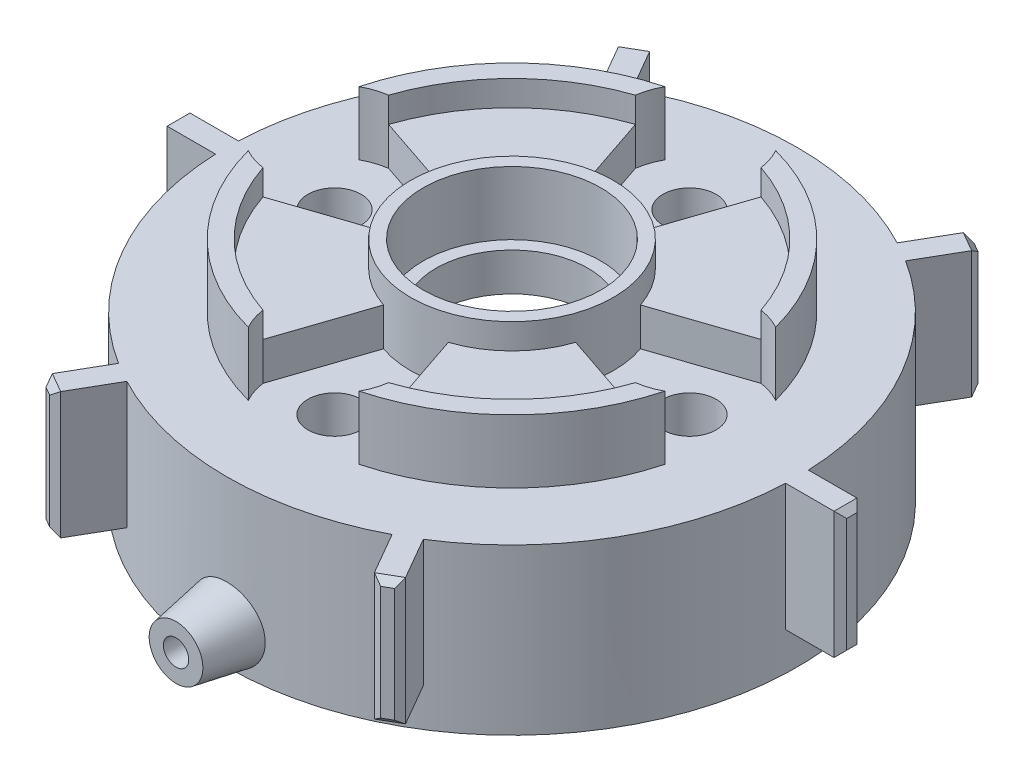
SolidWorks part; units mm, degrees
ref_plane "前视基准面" through (0, 0, 0) normal (0, 0, 1) x (1, 0, 0)
ref_plane "上视基准面" through (0, 0, 0) normal (0, 1, 0) x (1, 0, 0)
ref_plane "右视基准面" through (0, 0, 0) normal (1, 0, 0) x (0, 0, -1)
sketch "草图2" plane through (0, 0, 0) normal (0, 1, 0) x (1, 0, 0)
  line L0 (0, 30.8283) -> (0, -31.2236) construction
  line L1 (-31.2236, 0) -> (33.595, 0) construction
  circle A0 centre (0, 0) radius 22.5
  circle A1 centre (0, 0) radius 14 construction
  circle A2 centre (14, 0) radius 2.1
  circle A3 centre (0, 14) radius 2.1
  circle A4 centre (0, -14) radius 2.1
  circle A5 centre (-14, 0) radius 2.1
  circle A6 centre (0, 0) radius 6
  dimension "D1" = 45
  dimension "D2" = 4.2
  dimension "D3" = 4.2
  dimension "D4" = 28
  dimension "D5" = 12
extrude "凸台-拉伸1" add sketch "草图2" along normal blind 3
sketch "草图4" plane through (0, 0, 0) normal (0, -1, 0) x (1, 0, 0)
  circle A1 centre (0, 0) radius 22.5 construction
  circle A2 centre (0, 0) radius 22.5
  circle A3 centre (0, 0) radius 21
  dimension "D1" = 1.5
extrude "凸台-拉伸2" add sketch "草图4" along normal blind 10
sketch "草图5" plane through (0, 3, 0) normal (0, 1, 0) x (1, 0, 0)
  line L0 (-22.5, 0) -> (24.7317, 0) construction
  line L1 (0, 22.5) -> (0, -24.6712) construction
  line L2 (26.8, 0.9) -> (26.8, -0.9)
  line L3 (26.8, -0.9) -> (21, -0.9)
  line L4 (21, -0.9) -> (21, 0.9)
  line L5 (26.8, 0.9) -> (21, 0.9)
  line L6 (12.6206, -23.6595) -> (9.7206, -18.6365)
  line L7 (14.1794, -22.7595) -> (12.6206, -23.6595)
  line L8 (14.1794, -22.7595) -> (11.2794, -17.7365)
  line L9 (9.7206, -18.6365) -> (11.2794, -17.7365)
  line L10 (-14.1794, -22.7595) -> (-11.2794, -17.7365)
  line L11 (-12.6206, -23.6595) -> (-14.1794, -22.7595)
  line L12 (-12.6206, -23.6595) -> (-9.7206, -18.6365)
  line L13 (-11.2794, -17.7365) -> (-9.7206, -18.6365)
  line L14 (-26.8, 0.9) -> (-21, 0.9)
  line L15 (-26.8, -0.9) -> (-26.8, 0.9)
  line L16 (-26.8, -0.9) -> (-21, -0.9)
  line L17 (-21, 0.9) -> (-21, -0.9)
  line L18 (-12.6206, 23.6595) -> (-9.7206, 18.6365)
  line L19 (-14.1794, 22.7595) -> (-12.6206, 23.6595)
  line L20 (-14.1794, 22.7595) -> (-11.2794, 17.7365)
  line L21 (-9.7206, 18.6365) -> (-11.2794, 17.7365)
  line L22 (14.1794, 22.7595) -> (11.2794, 17.7365)
  line L23 (12.6206, 23.6595) -> (14.1794, 22.7595)
  line L24 (12.6206, 23.6595) -> (9.7206, 18.6365)
  line L25 (11.2794, 17.7365) -> (9.7206, 18.6365)
  circle A0 centre (0, 0) radius 22.5 construction
  point P14 (21, 0)
  point P15 (26.8, 0)
  dimension "D1" = 1.8
  dimension "D2" = 21
  dimension "D3" = 5.8
  dimension "D4" = 6
extrude "凸台-拉伸3" add sketch "草图5" against normal blind 10
sketch "草图6" plane through (0, 3, 0) normal (0, 1, 0) x (1, 0, 0)
  arc A0 (16.4286, 4.3706) -> (4.3706, 16.4286) centre (0, 0) ccw
  arc A1 (14.6875, 4.9525) -> (4.9525, 14.6875) centre (0, 0) ccw
  circle A2 centre (0, 0) radius 8
  circle A4 centre (0, 0) radius 7
  arc A7 (4.3706, -16.4286) -> (4.9525, -14.6875) centre (0, -14) ccw
  arc A8 (-14.6875, 4.9525) -> (-16.4286, 4.3706) centre (-14, 0) ccw
  arc A9 (16.4286, 4.3706) -> (14.6875, 4.9525) centre (14, 0) ccw
  arc A10 (4.9525, 14.6875) -> (4.3706, 16.4286) centre (0, 14) ccw
  arc A11 (14.6875, -4.9525) -> (16.4286, -4.3706) centre (14, 0) ccw
  arc A12 (4.3706, -16.4286) -> (16.4286, -4.3706) centre (0, 0) ccw
  arc A13 (4.9525, -14.6875) -> (14.6875, -4.9525) centre (0, 0) ccw
  arc A14 (-4.9525, -14.6875) -> (-4.3706, -16.4286) centre (0, -14) ccw
  arc A15 (-14.6875, -4.9525) -> (-4.9525, -14.6875) centre (0, 0) ccw
  arc A16 (-16.4286, -4.3706) -> (-14.6875, -4.9525) centre (-14, 0) ccw
  arc A17 (-16.4286, -4.3706) -> (-4.3706, -16.4286) centre (0, 0) ccw
  arc A18 (-4.9525, 14.6875) -> (-14.6875, 4.9525) centre (0, 0) ccw
  arc A19 (-4.3706, 16.4286) -> (-16.4286, 4.3706) centre (0, 0) ccw
  arc A20 (-4.3706, 16.4286) -> (-4.9525, 14.6875) centre (0, 14) ccw
  dimension "D1" = 16
  dimension "D2" = 1
  dimension "D3" = 31
  dimension "D4" = 1.5
  dimension "D5" = 10
  dimension "D6" = 10
  dimension "D7" = 10
  dimension "D8" = 10
extrude "凸台-拉伸4" add sketch "草图6" along normal blind 5
sketch "草图7" plane through (0, 3, 0) normal (0, 1, 0) x (1, 0, 0)
  line L0 (0, 22.5) -> (0, -29.8231) construction
  line L1 (29.3152, 0) -> (-30.7664, 0) construction
  line L2 (14.6875, -4.9525) -> (7.5806, -2.5561)
  line L3 (4.9525, -14.6875) -> (2.5561, -7.5806)
  line L4 (0, 0) -> (7.5806, -2.5561) construction
  line L5 (0, 0) -> (2.5561, -7.5806) construction
  line L6 (-4.9525, -14.6875) -> (-2.5561, -7.5806)
  line L7 (-14.6875, -4.9525) -> (-7.5806, -2.5561)
  line L8 (-14.6875, 4.9525) -> (-7.5806, 2.5561)
  line L9 (-4.9525, 14.6875) -> (-2.5561, 7.5806)
  line L10 (4.9525, 14.6875) -> (2.5561, 7.5806)
  line L11 (14.6875, 4.9525) -> (7.5806, 2.5561)
  arc A0 (10.4616, 19.92) -> (-10.4616, 19.92) centre (0, 0) ccw construction
  circle A1 centre (0, 0) radius 8 construction
  arc A2 (4.9525, -14.6875) -> (14.6875, -4.9525) centre (0, 0) ccw construction
  arc A4 (4.9525, -14.6875) -> (14.6875, -4.9525) centre (0, 0) ccw
  arc A5 (2.5561, -7.5806) -> (7.5806, -2.5561) centre (0, 0) ccw
  arc A6 (-2.5561, -7.5806) -> (-7.5806, -2.5561) centre (0, 0) cw
  arc A7 (-4.9525, -14.6875) -> (-14.6875, -4.9525) centre (0, 0) cw
  arc A8 (-4.9525, 14.6875) -> (-14.6875, 4.9525) centre (0, 0) ccw
  arc A9 (-2.5561, 7.5806) -> (-7.5806, 2.5561) centre (0, 0) ccw
  arc A10 (2.5561, 7.5806) -> (7.5806, 2.5561) centre (0, 0) cw
  arc A11 (4.9525, 14.6875) -> (14.6875, 4.9525) centre (0, 0) cw
extrude "凸台-拉伸5" add sketch "草图7" along normal blind 3
chamfer "倒角1" distance 0.5 angle 45 24 edges at (-12.6206, -2, 23.6595) (-13.4, -7, 23.2095) (-14.1794, -2, 22.7595) (-13.4, 3, 23.2095) (-26.8, -2, 0.9) (-26.8, -7, 0) (-26.8, -2, -0.9) (-26.8, 3, 0) (-14.1794, -2, -22.7595) (-13.4, -7, -23.2095) (-12.6206, -2, -23.6595) (-13.4, 3, -23.2095) (12.6206, -2, -23.6595) (13.4, -7, -23.2095) (14.1794, -2, -22.7595) (13.4, 3, -23.2095) (26.8, -2, -0.9) (26.8, -7, 0) (26.8, -2, 0.9) (26.8, 3, 0) (14.1794, -2, 22.7595) (13.4, -7, 23.2095) (12.6206, -2, 23.6595) (13.4, 3, 23.2095)
sketch "草图9" plane through (0, 0, 0) normal (0, 0, 1) x (1, 0, 0)
  line L0 (0, 0) -> (0, -17.9449) construction
  line L1 (-22.5, -10) -> (22.5, -10) construction
  circle A0 centre (0, -7) radius 3
  dimension "D1" = 6
  dimension "D2" = 3
extrude "凸台-拉伸6" add sketch "草图9" along normal blind 5 draft 10 from offset 21.5
sketch "草图10" plane through (0, 0, 26.5) normal (0, 0, 1) x (1, 0, 0)
  circle A0 centre (0, -7) radius 1
  dimension "D1" = 2
extrude "切除-拉伸1" cut sketch "草图10" against normal blind 5
